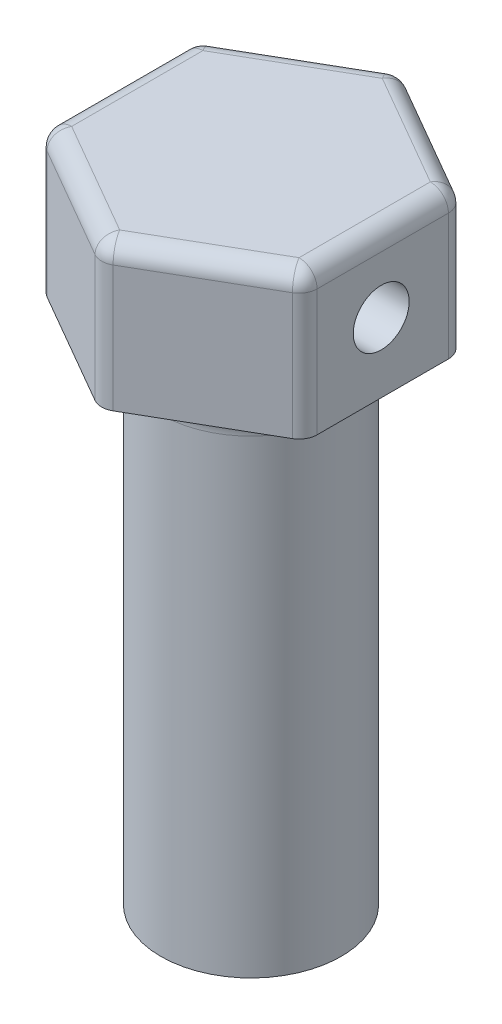
SolidWorks part; units mm, degrees
ref_plane "Front Plane" through (0, 0, 0) normal (0, 0, 1) x (1, 0, 0)
ref_plane "Top Plane" through (0, 0, 0) normal (0, 1, 0) x (1, 0, 0)
ref_plane "Right Plane" through (0, 0, 0) normal (1, 0, 0) x (0, 0, -1)
sketch "Sketch1" plane through (0, 0, 0) normal (0, 1, 0) x (1, 0, 0)
  line L1 (7.3, -4.2147) -> (7.3, 4.2147)
  line L2 (7.3, 4.2147) -> (0, 8.4293)
  line L3 (0, 8.4293) -> (-7.3, 4.2147)
  line L4 (-7.3, 4.2147) -> (-7.3, -4.2147)
  line L5 (-7.3, -4.2147) -> (0, -8.4293)
  line L6 (0, -8.4293) -> (7.3, -4.2147)
  circle A0 centre (0, 0) radius 7.3 construction
  dimension "D1" = 14.6
extrude "Boss-Extrude1" add sketch "Sketch1" along normal blind 8
sketch "Sketch2" plane through (0, 0, 0) normal (0, -1, 0) x (1, 0, 0)
  line L0 (-1.55, 1.3416) -> (-1.55, -1.3416)
  line L1 (-7.3, -4.2147) -> (-7.3, 4.2147) construction
  arc A0 (-1.55, -1.3416) -> (-1.55, 1.3416) centre (0, 0) ccw
  circle A1 centre (0, 0) radius 5
  dimension "D1" = 4.1
  dimension "D2" = 10
  dimension "D3" = 1.55
extrude "Boss-Extrude2" add sketch "Sketch2" along normal blind 28 contours A1 | A0 L0
fillet "Fillet1" radius 2 1 edges at (0, 0, 5)
sketch "Sketch3" plane through (7.3, 0, 0) normal (1, 0, 0) x (0, 0, -1)
  line L0 (-7, 0) -> (7, 0) construction
  line L1 (4.2147, 8) -> (4.2147, 0) construction
  circle A0 centre (-0.0853, 3.85) radius 1.55
  dimension "D1" = 3.1
  dimension "D2" = 3.85
  dimension "D3" = 4.3
extrude "Cut-Extrude1" cut sketch "Sketch3" against normal through all
fillet "Fillet2" radius 1 12 edges at (-3.65, 8, 6.322) (-7.3, 8, 0) (-3.65, 8, -6.322) (3.65, 8, -6.322) (7.3, 8, 0) (3.65, 8, 6.322) (-7.3, 4, -4.2147) (0, 4, -8.4293) (7.3, 4, -4.2147) (7.3, 4, 4.2147) (0, 4, 8.4293) (-7.3, 4, 4.2147)
sketch "Sketch4" plane through (0, 0, 0) normal (1, 0, 0) x (0, 0, -1)
  line L1 (-16.1086, 1.5942) -> (18.1695, 1.5942)
  line L2 (-16.1086, 1.5942) -> (-16.1086, -34.824)
  line L3 (-16.1086, -34.824) -> (18.1695, -34.824)
  line L4 (18.1695, 1.5942) -> (18.1695, -34.824)
extrude "Cut-Extrude2" [suppressed] cut sketch "Sketch4" against normal through all both and the other way through all
sketch "Sketch5" plane through (0, -28, 0) normal (0, -1, 0) x (1, 0, 0)
  circle A0 centre (0, 0) radius 2.05
  dimension "D1" = 4.1
extrude "Cut-Extrude3" cut sketch "Sketch5" against normal blind 4
equation "\"1.ø15\"=1.5"
